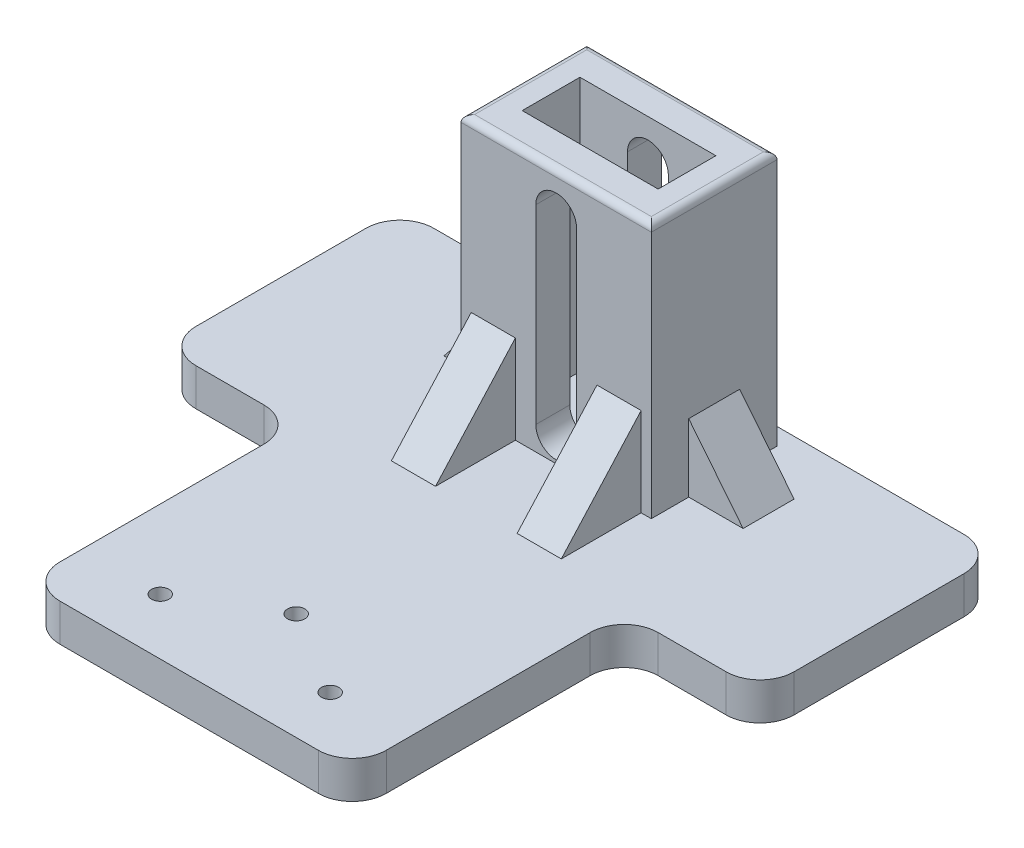
SolidWorks part; units mm, degrees
ref_plane "前视基准面" through (0, 0, 0) normal (0, 0, 1) x (1, 0, 0)
ref_plane "上视基准面" through (0, 0, 0) normal (0, 1, 0) x (1, 0, 0)
ref_plane "右视基准面" through (0, 0, 0) normal (1, 0, 0) x (0, 0, -1)
other "Configuration Table"
sketch "草图1" plane through (0, 0, 0) normal (0, 1, 0) x (1, 0, 0)
  line L0 (-13.1497, 50.7938) -> (-13.1497, -28.9315) construction
  line L1 (-61.1497, 43.7897) -> (34.8503, 43.7897)
  line L5 (-48.1497, 43.7897) -> (21.8503, 43.7897)
  line L6 (-48.1497, 43.7897) -> (-48.1497, -28.9315) construction
  line L8 (21.8503, 43.7897) -> (21.8503, -28.9315) construction
  line L10 (-61.1497, 43.7897) -> (34.8503, 43.7897)
  line L11 (-61.1497, 43.7897) -> (-61.1497, -26.2103)
  line L12 (-61.1497, -26.2103) -> (34.8503, -26.2103)
  line L13 (34.8503, 43.7897) -> (34.8503, -26.2103)
  circle A0 centre (-48.1497, 34.7897) radius 3
  circle A1 centre (21.8503, 34.7897) radius 3
  circle A2 centre (-48.1497, -15.2103) radius 3
  circle A3 centre (21.8503, -15.2103) radius 3
  circle A4 centre (-48.1497, 4.7897) radius 3
  circle A5 centre (21.8503, 4.7897) radius 3
  dimension "D4" = 9
  dimension "D5" = 9
  dimension "D6" = 50
  dimension "D7" = 50
  dimension "D8" = 35
  dimension "D10" = 20
  dimension "D11" = 20
  dimension "D12" = 6
  dimension "D13" = 6
  dimension "D14" = 6
  dimension "D15" = 6
  dimension "D16" = 6
  dimension "6" = 6
  dimension "D1" = 48
  dimension "D2" = 48
  dimension "D3" = 70
  dimension "D9" = 35
extrude "凸台-拉伸1" add sketch "草图1" along normal blind 6 contours L13 L1 L11 L12 A5 A4 A3 A2 A1 A0 | A4 | A0 | A2 | A3 | A5 | A1 region at (-13.1497, 0, -8.807)
sketch "草图2" plane through (0, 6, 0) normal (0, 1, 0) x (1, 0, 0)
  line L0 (-13.1497, 47.7191) -> (-13.1497, -35.4795) construction
  line L1 (-61.1497, 43.7897) -> (-61.1497, -26.2103) construction
  line L2 (-61.1497, 43.7897) -> (34.8503, 43.7897) construction
  line L3 (-33.1497, 28.7897) -> (6.8503, 28.7897)
  line L4 (-33.1497, 28.7897) -> (-33.1497, 11.7897)
  line L5 (-33.1497, 11.7897) -> (6.8503, 11.7897)
  line L6 (6.8503, 28.7897) -> (6.8503, 11.7897)
  line L7 (-33.1497, 28.7897) -> (6.8503, 11.7897) construction
  line L8 (-33.1497, 11.7897) -> (6.8503, 28.7897) construction
  line L9 (34.8503, 43.7897) -> (34.8503, -26.2103) construction
  line L11 (-41.1497, 38.7897) -> (14.8503, 38.7897)
  line L12 (-41.1497, 38.7897) -> (-41.1497, 1.7897)
  line L13 (-41.1497, 1.7897) -> (14.8503, 1.7897)
  line L14 (14.8503, 38.7897) -> (14.8503, 1.7897)
  line L15 (-41.1497, 38.7897) -> (14.8503, 1.7897) construction
  line L16 (-41.1497, 1.7897) -> (14.8503, 38.7897) construction
  point P4 (-13.1497, 20.2897)
  point P13 (-13.1497, 20.2897)
  dimension "D1" = 48
  dimension "D2" = 40
  dimension "D3" = 17
  dimension "D4" = 15
  dimension "D5" = 48
  dimension "D6" = 10
  dimension "D7" = 8
extrude "凸台-拉伸2" add sketch "草图2" along normal blind 80
sketch "草图3" plane through (14.8503, 0, 0) normal (1, 0, 0) x (0, 0, -1)
  line L0 (20.2897, 86) -> (20.2897, -3.5497) construction
  line L1 (1.7897, 86) -> (38.7897, 86) construction
sketch "草图4" plane through (-41.1497, 0, 0) normal (-1, 0, 0) x (0, 0, 1)
  line L0 (-20.2897, 86) -> (-20.2897, -3.5497) construction
ref_plane "基准面1" through (0, 0, -20.2897) normal (0, 0, 1) x (1, 0, 0)
sketch "草图5" plane through (0, 0, -20.2897) normal (0, 0, 1) x (1, 0, 0)
  line L0 (-61.1497, 6) -> (-41.1497, 31)
  line L1 (-41.1497, 86) -> (-41.1497, -3.5497) construction
  line L2 (-41.1497, 31) -> (-41.1497, 6)
  line L3 (-41.1497, 6) -> (-61.1497, 6)
  line L4 (14.8503, 31) -> (34.8503, 6)
  line L5 (14.8503, 86) -> (14.8503, -3.5497) construction
  line L6 (34.8503, 6) -> (14.8503, 6)
  line L7 (14.8503, 31) -> (14.8503, 6)
  dimension "D1" = 25
  dimension "D2" = 25
extrude "凸台-拉伸3" add sketch "草图5" along normal mid plane 15
sketch "草图6" plane through (0, 0, -1.7897) normal (0, 0, 1) x (1, 0, 0)
  line L0 (-13.1497, 86) -> (-13.1497, -11.8788) construction
  line L1 (-41.1497, 86) -> (14.8503, 86) construction
sketch "草图7" plane through (0, 0, -38.7897) normal (0, 0, -1) x (-1, 0, 0)
  line L0 (13.1497, 86) -> (13.1497, -11.8788) construction
  line L1 (-14.8503, 86) -> (41.1497, 86) construction
ref_plane "基准面2" through (-13.1497, 0, 0) normal (1, 0, 0) x (0, 0, -1)
sketch "草图8" plane through (-13.1497, 0, 0) normal (1, 0, 0) x (0, 0, -1)
  line L0 (-26.2103, 6) -> (1.7897, 37.0606)
  line L1 (1.7897, 86) -> (1.7897, -11.8788) construction
  line L2 (1.7897, 37.0606) -> (1.7897, 6)
  line L3 (1.7897, 6) -> (-26.2103, 6)
extrude "凸台-拉伸4" add sketch "草图8" along normal mid plane 50
sketch "草图9" plane through (0, 0, -38.7897) normal (0, 0, -1) x (-1, 0, 0)
  line L0 (13.1497, 74) -> (13.1497, 18) construction
  line L1 (13.1497, 86) -> (13.1497, -11.8788) construction
  line L2 (19.1497, 74) -> (19.1497, 18)
  line L3 (7.1497, 74) -> (7.1497, 18)
  line L4 (-14.8503, 86) -> (41.1497, 86) construction
  line L5 (-14.8503, 6) -> (41.1497, 6) construction
  arc A0 (19.1497, 74) -> (7.1497, 74) centre (13.1497, 74) ccw
  arc A1 (7.1497, 18) -> (19.1497, 18) centre (13.1497, 18) ccw
  point P4 (13.1497, 46)
  dimension "D3" = 12
  dimension "D1" = 12
  dimension "D2" = 12
extrude "切除-拉伸1" cut sketch "草图9" against normal through all
sketch "草图10" plane through (0, 86, 0) normal (0, 1, 0) x (1, 0, 0)
  line L0 (-19.1497, 1.7897) -> (-38.1497, 1.7897) construction
  line L1 (-25.1497, 1.7897) -> (-1.1497, 1.7897)
  line L2 (-25.1497, 1.7897) -> (-25.1497, -29.1186)
  line L3 (-25.1497, -29.1186) -> (-1.1497, -29.1186)
  line L4 (-1.1497, 1.7897) -> (-1.1497, -29.1186)
  line L5 (-13.1497, -20.35) -> (-13.1497, 20.35) construction
  dimension "D1" = 12
  dimension "D2" = 24
extrude "切除-拉伸2" cut sketch "草图10" against normal up to surface (80 mm away) up to face at (20.5169, 6, 3.8769)
fillet "圆角1" radius 2 4 edges at (-13.1497, 86, -38.7897) (14.8503, 86, -20.2897) (-41.1497, 86, -20.2897) (-13.1497, 86, -1.7897)
sketch "草图11" plane through (0, 0, 0) normal (0, -1, 0) x (1, 0, 0)
  line L0 (-39.1497, -20.2897) -> (48.9342, -20.2897) construction
  line L1 (-61.1497, -43.7897) -> (34.8503, -43.7897)
  line L2 (-61.1497, -43.7897) -> (-61.1497, 106.2103)
  line L3 (-61.1497, 106.2103) -> (34.8503, 106.2103)
  line L4 (34.8503, -43.7897) -> (34.8503, 106.2103)
  line L6 (-101.1497, 26.2103) -> (74.8503, 26.2103)
  line L7 (-101.1497, 26.2103) -> (-101.1497, -43.7897)
  line L8 (12.8503, -36.7897) -> (12.8503, -3.7897)
  line L9 (-39.1497, -36.7897) -> (12.8503, -36.7897)
  line L10 (-39.1497, -3.7897) -> (-39.1497, -36.7897)
  line L11 (12.8503, -3.7897) -> (-39.1497, -3.7897)
  line L12 (12.8503, -36.7897) -> (12.8503, -3.7897)
  line L13 (-39.1497, -36.7897) -> (12.8503, -36.7897)
  line L14 (-39.1497, -3.7897) -> (-39.1497, -36.7897)
  line L15 (12.8503, -3.7897) -> (-39.1497, -3.7897)
  line L16 (-101.1497, -43.7897) -> (74.8503, -43.7897)
  line L17 (74.8503, 26.2103) -> (74.8503, -43.7897)
  circle A0 centre (-38.1497, 89.7103) radius 2.55
  circle A1 centre (11.8503, 89.7103) radius 2.55
  circle A2 centre (-13.1497, 74.7103) radius 2.55
  line M18 (34.8503, -43.7897) -> (34.8503, 26.2103)
  line M19 (34.8503, 26.2103) -> (-61.1497, 26.2103)
  line M20 (-61.1497, 26.2103) -> (-61.1497, -43.7897)
  line M21 (-61.1497, -43.7897) -> (34.8503, -43.7897)
  dimension "D2" = 110
  dimension "D3" = 110
  dimension "D5" = 5.1
  dimension "D6" = 5.1
  dimension "D7" = 5.1
  dimension "D8" = 15
  dimension "D9" = 25
  dimension "D10" = 25
  dimension "D12" = 48
  dimension "D4" = 150
  dimension "D11" = 96
  dimension "D13" = 40
  dimension "D14" = 40
  dimension "D1" = 0
extrude "凸台-拉伸5" add sketch "草图11" against normal up to surface (6 mm away) contours L4 L3 L2 A2 A1 A0 M19 | L17 L6 L4 L16 M18 | L7 L16 L6 M20 | L15 L12 L4 L13 L14 M19 M20 M21 M18 | L0 L14 L13 L12 region at (33.6622, 0, -32.0397) region at (54.8503, 0, -8.7897) region at (-13.1497, 0, -28.5397) region at (-13.1497, 0, 66.0615) region at (-81.1497, 0, -8.7897) up to face at (-46.8164, 6, 3.8769)
fillet "圆角2" radius 10 8 edges at (-61.1497, 3, 26.2103) (-101.1497, 3, -43.7897) (74.8503, 3, -43.7897) (74.8503, 3, 26.2103) (34.8503, 3, 26.2103) (34.8503, 3, 106.2103) (-61.1497, 3, 106.2103) (-101.1497, 3, 26.2103)
sketch "草图12" plane through (0, 6, 0) normal (0, 1, 0) x (1, 0, 0)
  line L0 (14.8503, 1.7897) -> (14.8503, 38.7897) construction
  line L1 (11.8503, 1.7897) -> (14.8503, 1.7897)
  line L2 (-41.1497, 1.7897) -> (14.8503, 1.7897) construction
  line L4 (14.8503, 27.7897) -> (14.8503, 12.7897)
  line L6 (-38.1497, 1.7897) -> (11.8503, 1.7897)
  line L8 (64.8503, 43.7897) -> (-91.1497, 43.7897)
  line L9 (-101.1497, 33.7897) -> (-101.1497, -16.2103)
  line L10 (-91.1497, -26.2103) -> (-71.1497, -26.2103)
  line L11 (-61.1497, -36.2103) -> (-61.1497, -96.2103)
  line L12 (-51.1497, -106.2103) -> (24.8503, -106.2103)
  line L13 (34.8503, -96.2103) -> (34.8503, -36.2103)
  line L14 (44.8503, -26.2103) -> (64.8503, -26.2103)
  line L15 (74.8503, -16.2103) -> (74.8503, 33.7897)
  line L16 (64.8503, 43.7897) -> (-91.1497, 43.7897)
  line L17 (-101.1497, 33.7897) -> (-101.1497, -16.2103)
  line L18 (-91.1497, -26.2103) -> (-71.1497, -26.2103)
  line L19 (-61.1497, -36.2103) -> (-61.1497, -96.2103)
  line L20 (-51.1497, -106.2103) -> (24.8503, -106.2103)
  line L21 (34.8503, -96.2103) -> (34.8503, -36.2103)
  line L22 (44.8503, -26.2103) -> (64.8503, -26.2103)
  line L23 (74.8503, -16.2103) -> (74.8503, 33.7897)
  line L36 (34.8503, 12.7897) -> (34.8503, 27.7897)
  line L44 (34.8503, 27.7897) -> (14.8503, 27.7897)
  line L45 (14.8503, 27.7897) -> (14.8503, 12.7897)
  line L46 (14.8503, 12.7897) -> (34.8503, 12.7897)
  line L48 (34.8503, 27.7897) -> (14.8503, 27.7897)
  line L52 (14.8503, 38.7897) -> (-41.1497, 38.7897) construction
  line L54 (-25.1497, 1.7897) -> (-1.1497, 1.7897)
  line L55 (-41.1497, 38.7897) -> (-41.1497, 1.7897) construction
  line L56 (14.8503, 1.7897) -> (14.8503, 12.7897)
  line L58 (-41.1497, 1.7897) -> (-38.1497, 1.7897)
  line L60 (14.8503, 38.7897) -> (-41.1497, 38.7897)
  line L63 (-41.1497, 38.7897) -> (-41.1497, 27.7897)
  line L64 (-41.1497, 12.7897) -> (-41.1497, 1.7897)
  line L65 (14.8503, 27.7897) -> (14.8503, 38.7897)
  line L66 (-41.1497, 27.7897) -> (-41.1497, 12.7897)
  line L67 (14.8503, 27.7897) -> (14.8503, 12.7897)
  circle A0 centre (11.8503, -89.7103) radius 2.55 construction
  circle A1 centre (-13.1497, -74.7103) radius 2.55 construction
  circle A2 centre (-38.1497, -89.7103) radius 2.55 construction
  circle A3 centre (11.8503, -89.7103) radius 2.55
  circle A4 centre (-13.1497, -74.7103) radius 2.55
  circle A5 centre (-38.1497, -89.7103) radius 2.55
  arc A8 (-91.1497, 43.7897) -> (-101.1497, 33.7897) centre (-91.1497, 33.7897) ccw
  arc A9 (-101.1497, -16.2103) -> (-91.1497, -26.2103) centre (-91.1497, -16.2103) ccw
  arc A10 (-61.1497, -36.2103) -> (-71.1497, -26.2103) centre (-71.1497, -36.2103) ccw
  arc A11 (-61.1497, -96.2103) -> (-51.1497, -106.2103) centre (-51.1497, -96.2103) ccw
  arc A12 (24.8503, -106.2103) -> (34.8503, -96.2103) centre (24.8503, -96.2103) ccw
  arc A13 (44.8503, -26.2103) -> (34.8503, -36.2103) centre (44.8503, -36.2103) ccw
  arc A14 (64.8503, -26.2103) -> (74.8503, -16.2103) centre (64.8503, -16.2103) ccw
  arc A15 (74.8503, 33.7897) -> (64.8503, 43.7897) centre (64.8503, 33.7897) ccw
  arc A16 (-91.1497, 43.7897) -> (-101.1497, 33.7897) centre (-91.1497, 33.7897) ccw
  arc A17 (-101.1497, -16.2103) -> (-91.1497, -26.2103) centre (-91.1497, -16.2103) ccw
  arc A18 (-61.1497, -36.2103) -> (-71.1497, -26.2103) centre (-71.1497, -36.2103) ccw
  arc A19 (-61.1497, -96.2103) -> (-51.1497, -106.2103) centre (-51.1497, -96.2103) ccw
  arc A20 (24.8503, -106.2103) -> (34.8503, -96.2103) centre (24.8503, -96.2103) ccw
  arc A21 (44.8503, -26.2103) -> (34.8503, -36.2103) centre (44.8503, -36.2103) ccw
  arc A22 (64.8503, -26.2103) -> (74.8503, -16.2103) centre (64.8503, -16.2103) ccw
  arc A23 (74.8503, 33.7897) -> (64.8503, 43.7897) centre (64.8503, 33.7897) ccw
  dimension "D1" = 0
  dimension "D5" = 0
extrude "凸台-拉伸6" add sketch "草图12" along direction (0, 1, 0) on the side of the normal blind 5 contours L16 A16 L17 A17 L18 A18 L19 A19 L20 A20 L21 A21 L22 A22 L23 A23 | A5 | A4 | A3
sketch "草图13" plane through (0, 11, 0) normal (0, 1, 0) x (1, 0, 0)
  line L0 (-83.0604, -47.6221) -> (51.4758, -47.6221)
  line L1 (-83.0604, -47.6221) -> (-83.0604, -110.9986)
  line L2 (51.4758, -47.6221) -> (51.4758, -110.9986)
  line L3 (-83.0604, -110.9986) -> (51.4758, -110.9986)
